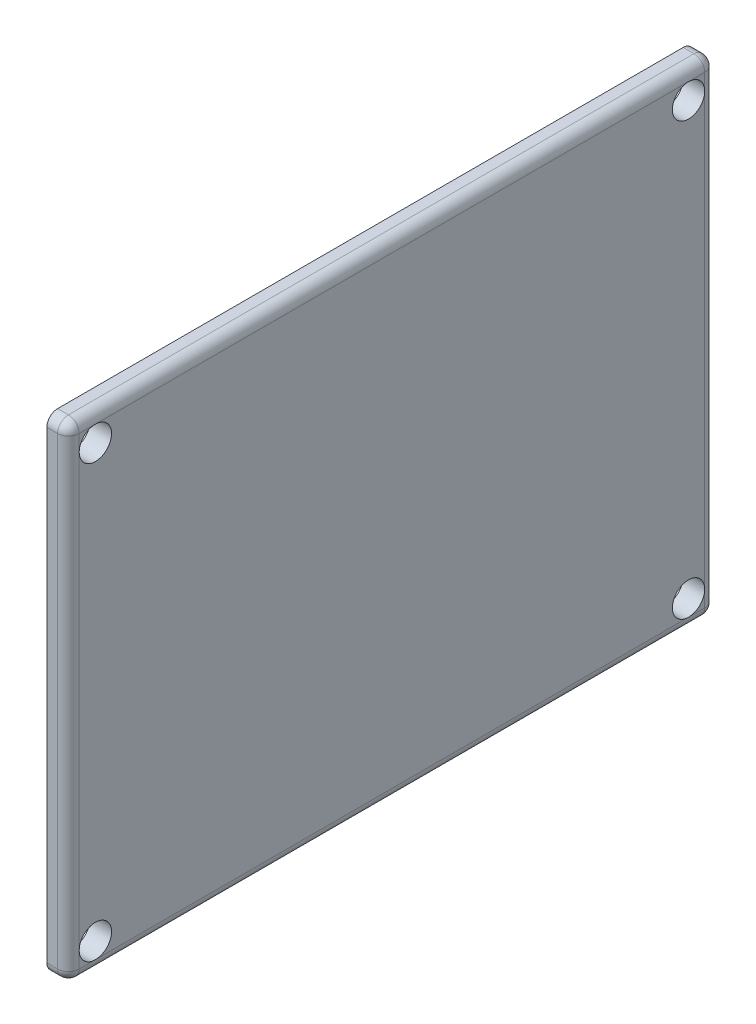
SolidWorks part; units mm, degrees
ref_plane "Front Plane" through (0, 0, 0) normal (0, 0, 1) x (1, 0, 0)
ref_plane "Top Plane" through (0, 0, 0) normal (0, 1, 0) x (1, 0, 0)
ref_plane "Right Plane" through (0, 0, 0) normal (1, 0, 0) x (0, 0, -1)
sketch "Sketch1" plane through (0, 0, 0) normal (1, 0, 0) x (0, 0, -1)
  line L1 (-30, -22.5) -> (30, -22.5)
  line L2 (-30, -22.5) -> (-30, 22.5)
  line L3 (-30, 22.5) -> (30, 22.5)
  line L4 (30, -22.5) -> (30, 22.5)
  line L5 (-30, -22.5) -> (30, 22.5) construction
  line L6 (-30, 22.5) -> (30, -22.5) construction
  point P0 (0, 0)
  dimension "D1" = 60
  dimension "D2" = 45
extrude "Boss-Extrude1" add sketch "Sketch1" along normal blind 2
hole_wizard "Ø3.0mm Dowel Hole1" positions "Sketch2" profile "Sketch3" hole size "Ø3.0" standard "ANSI Metric"
sketch "Sketch2" plane through (2, 0, 0) normal (1, 0, 0) x (0, 0, -1)
  line L0 (30, 22.5) -> (-30, 22.5) construction
  line L1 (-30, 22.5) -> (-30, -22.5) construction
  line L2 (-30, -22.5) -> (30, -22.5) construction
  line L3 (30, -22.5) -> (30, 22.5) construction
  point P0 (-27.5, 20)
  point P2 (27.5, 20)
  point P4 (27.5, -20)
  point P6 (-27.5, -20)
  point P9 (0, 0)
  point P10 (0, 0)
  point P11 (0, 0)
  point P12 (0, 0)
  dimension "D1" = 2.5
  dimension "D2" = 2.5
  dimension "D3" = 2.5
  dimension "D4" = 2.5
sketch "Sketch3" plane through (2, 20, 27.5) normal (0, 1, 0) x (0, 0, -1)
  line L0 (0, 0) -> (0, 20.9013)
  line L1 (0, 20.9013) -> (1.5, 20)
  line L2 (1.5, 20) -> (1.5, 0)
  line L5 (1.5, 0) -> (0, 0)
  line L10 (0, 20.9013) -> (-1.5, 20) construction
  line L11 (0, -6.35) -> (0, 107.95) construction
  dimension "Hole Dia." = 3
  dimension "Hole Depth" = 20
  dimension "Drill Angle" = 118
fillet "Fillet2" radius 1 4 edges at (1, -22.5, -30) (1, -22.5, 30) (1, 22.5, -30) (1, 22.5, 30)
fillet "Fillet1" radius 1 8 edges at (2, 0, -30) (2, -22.5, 0) (2, 22.5, 0) (2, 0, 30) (2, 22.2071, 29.7071) (2, 22.2071, -29.7071) (2, -22.2071, -29.7071) (2, -22.2071, 29.7071)
equation "\"D2@Sketch2\"=\"D1@Sketch2\""
equation "\"D3@Sketch2\"=\"D1@Sketch2\""
equation "\"D4@Sketch2\"=\"D1@Sketch2\""
